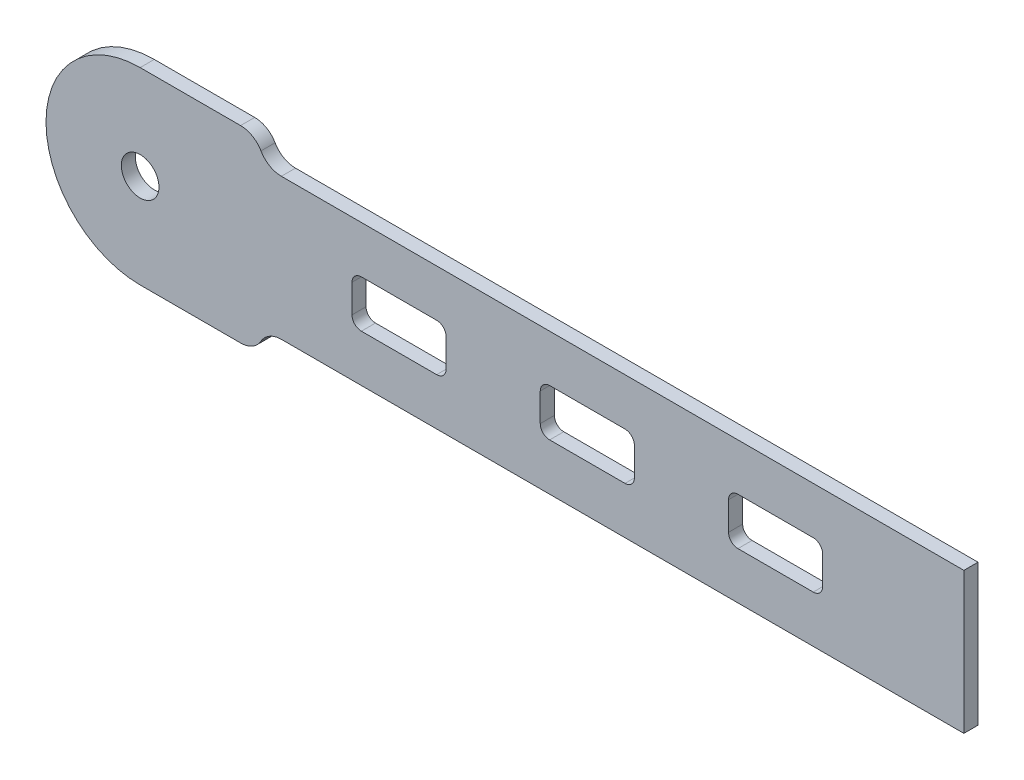
SolidWorks part; units mm, degrees
ref_plane "Front Plane" through (0, 0, 0) normal (0, 0, 1) x (1, 0, 0)
ref_plane "Top Plane" through (0, 0, 0) normal (0, 1, 0) x (1, 0, 0)
ref_plane "Right Plane" through (0, 0, 0) normal (1, 0, 0) x (0, 0, -1)
sketch "Sketch1" plane through (0, 0, 0) normal (0, 0, 1) x (1, 0, 0)
  line L0 (-50, -25) -> (-50, -15)
  line L1 (-50, -25) -> (-100, -25)
  line L2 (100, -15) -> (100, 15)
  line L3 (-50, 25) -> (-100, 25)
  line L4 (-100, -25) -> (-100, 25)
  line L5 (100, 15) -> (-100, 15) construction
  line L6 (-50, 15) -> (-50, 25)
  line L7 (100, 15) -> (-50, 15)
  line L8 (100, -15) -> (-50, -15)
  line L9 (100, -15) -> (-100, -15) construction
  line L10 (100, -25) -> (-100, -25) construction
  line L11 (100, 25) -> (-100, 25) construction
  line L12 (-50, -25) -> (-50, 25) construction
  circle A0 centre (-75, 0) radius 4
  point P0 (0, 0)
extrude "Boss-Extrude1" add sketch "Sketch1" along normal blind 3
fillet "Fillet1" radius 5 4 edges at (-50, -25, 1.5) (-50, -15, 1.5) (-50, 15, 1.5) (-50, 25, 1.5)
sketch "Sketch2" plane through (0, 0, 0) normal (0, 0, -1) x (-1, 0, 0)
  line L1 (30, -5) -> (30, 5)
  line L2 (-10, -5) -> (-30, -5)
  line L3 (10, 5) -> (30, 5)
  line L4 (10, -5) -> (10, 5)
  line L5 (-10, -5) -> (-10, 5)
  line L6 (-30, -5) -> (-30, 5)
  line L7 (-50, -5) -> (-50, 5)
  line L8 (-70, -5) -> (-70, 5)
  line L12 (-100, 5) -> (45, 5)
  line L13 (-70, 5) -> (-50, 5)
  line L14 (-50, -5) -> (-70, -5)
  line L15 (45, -5) -> (-100, -5)
  line L16 (30, -5) -> (10, -5)
  line L17 (-30, 5) -> (-10, 5)
  dimension "D2" = 10
  dimension "D3" = 10
extrude "Cut-Extrude1" cut sketch "Sketch2" against normal blind 3
fillet "Fillet2" radius 2 12 edges at (50, 5, 1.5) (50, -5, 1.5) (70, -5, 1.5) (70, 5, 1.5) (30, 5, 1.5) (30, -5, 1.5) (10, -5, 1.5) (10, 5, 1.5) (-30, 5, 1.5) (-10, 5, 1.5) (-10, -5, 1.5) (-30, -5, 1.5)
sketch "Sketch3" plane through (0, 0, 0) normal (0, 0, -1) x (-1, 0, 0)
  line L0 (55, 25) -> (100, 25) construction
  line L1 (100, 25) -> (100, -25) construction
  line L2 (100, -25) -> (55, -25) construction
  line L3 (55, 25) -> (100, 25)
  line L4 (100, 25) -> (100, -25)
  line L5 (100, -25) -> (75, -25)
  line L9 (75, 20) -> (50, 20)
  line L10 (100, -25) -> (55, -25)
  line L11 (75, -20) -> (50, -20)
  line L12 (55, 25) -> (100, 25)
  arc A0 (75, -20) -> (75, 20) centre (75, 0) ccw
  arc A1 (50, -20) -> (55, -25) centre (55, -20) ccw construction
  arc A2 (55, 25) -> (50, 20) centre (55, 20) ccw construction
  arc A3 (50, -20) -> (55, -25) centre (55, -20) ccw
  arc A4 (55, 25) -> (50, 20) centre (55, 20) ccw
  arc M28 (50, -20) -> (55, -25) centre (55, -20) ccw
  line M29 (55, -25) -> (100, -25)
  line M30 (100, -25) -> (100, 25)
  line M31 (100, 25) -> (55, 25)
  arc M32 (55, 25) -> (50, 20) centre (55, 20) ccw
extrude "Cut-Extrude3" cut sketch "Sketch3" against normal blind 3 contours A0 L11 L9 M28 M29 M30 M31 M32 region at (-77.5, 24.2929, 0) body kept at (-75, -20, 0)
fillet "Fillet4" radius 5 2 edges at (-50, -20, 1.5) (-50, 20, 1.5)
